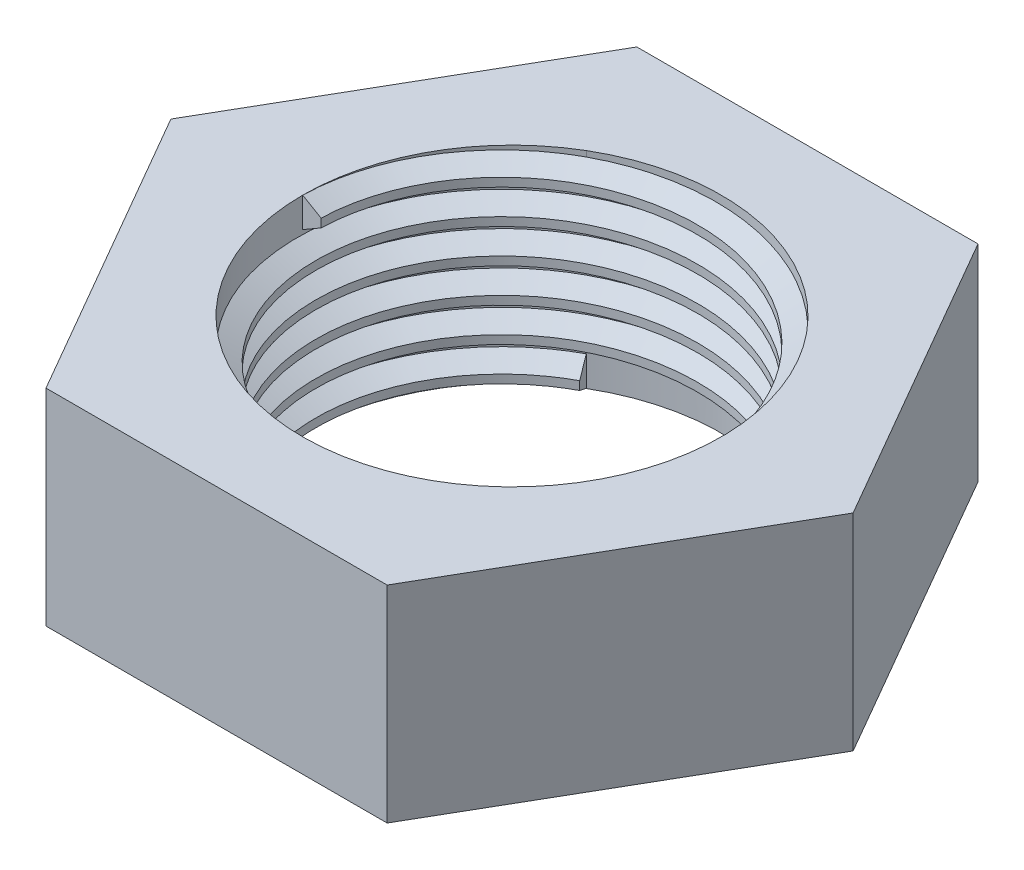
SolidWorks part; units mm, degrees
ref_plane "前视基准面" through (0, 0, 0) normal (0, 0, 1) x (1, 0, 0)
ref_plane "上视基准面" through (0, 0, 0) normal (0, 1, 0) x (1, 0, 0)
ref_plane "右视基准面" through (0, 0, 0) normal (1, 0, 0) x (0, 0, -1)
sketch "草图1" plane through (0, 0, 0) normal (0, 1, 0) x (1, 0, 0)
  line L0 (0, 0) -> (10.0722, 0) construction
  line L1 (3.9722, 6.88) -> (-3.9722, 6.88)
  line L2 (-3.9722, 6.88) -> (-7.9443, 0)
  line L3 (-7.9443, 0) -> (-3.9722, -6.88)
  line L4 (-3.9722, -6.88) -> (3.9722, -6.88)
  line L5 (3.9722, -6.88) -> (7.9443, 0)
  line L6 (7.9443, 0) -> (3.9722, 6.88)
  circle A0 centre (0, 0) radius 6.88 construction
  circle A1 centre (0, 0) radius 4.875
  dimension "D2" = 9.75
  dimension "D1" = 13.76
extrude "凸台-拉伸1" add sketch "草图1" along normal blind 4.8
thread "螺纹线1" pitch 0.7937 method extrude profile "螺纹线轮廓2" start angle 0, offset 0, length 4.1, pitch 0.7937, diameter 9.75
ref_plane "基准面2" through (-4.875, 4.8, 0) normal (0, 0, 1) x (-1, 0, 0)
sketch "螺纹线轮廓2" plane through (-4.875, 4.8, 0) normal (0, 0, 1) x (-1, 0, 0)
  line L0 (0, 0) -> (0, 0.7937) construction
  line L11 (0, 0) -> (0, 0.6945)
  line L12 (0, 0.6945) -> (-0.4296, 0.4465)
  line L13 (-0.4296, 0.4465) -> (-0.4296, 0.248)
  line L15 (-0.4296, 0.248) -> (0, 0)
  line L17 (-0.4296, 0.3473) -> (0, 0.3473) construction
  point P2 (0, 0)
  dimension "Pitch" = 0.7937
  dimension "Profile_Angle" = 60
  dimension "Profile_Land" = 0.1984
  dimension "Profile_Height" = 0.4296
